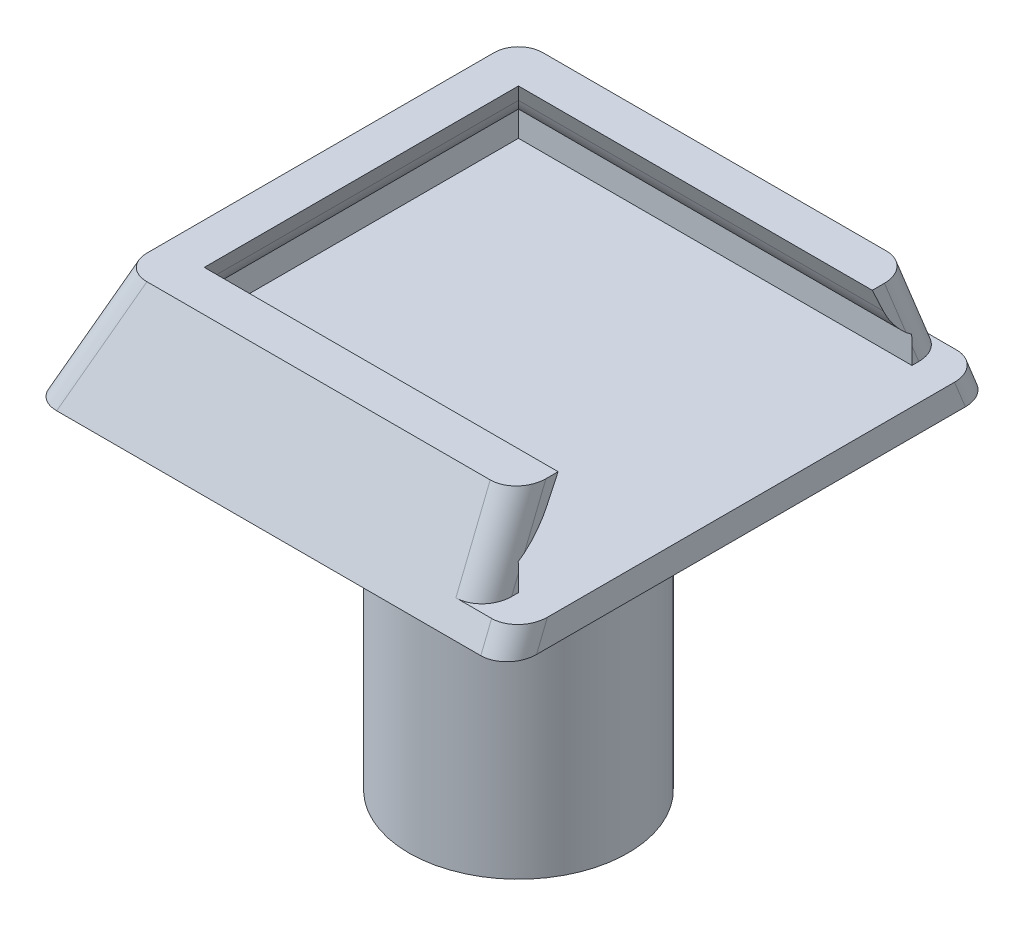
SolidWorks part; units mm, degrees
ref_plane "Front Plane" through (0, 0, 0) normal (0, 0, 1) x (1, 0, 0)
ref_plane "Top Plane" through (0, 0, 0) normal (0, 1, 0) x (1, 0, 0)
ref_plane "Right Plane" through (0, 0, 0) normal (1, 0, 0) x (0, 0, -1)
sketch "Sketch1" plane through (0, 0, 0) normal (0, 1, 0) x (1, 0, 0)
  line L1 (0, 0) -> (52, 0)
  line L2 (0, 0) -> (0, 52)
  line L3 (0, 52) -> (52, 52)
  line L4 (52, 0) -> (52, 52)
  dimension "D1" = 52
  dimension "D2" = 52
extrude "Boss-Extrude1" add sketch "Sketch1" along normal blind 3
sketch "Sketch2" plane through (0, 0, 0) normal (0, -1, 0) x (-1, 0, 0)
  line L0 (0, 0) -> (-52, 0) construction
  line L1 (0, 52) -> (0, 0) construction
  circle A0 centre (-26, 26) radius 12.25
  circle A1 centre (-26, 26) radius 10.75
  point P6 (-26, 0)
  point P9 (0, 26)
  dimension "D1" = 21.5
  dimension "D2" = 24.5
extrude "Boss-Extrude2" add sketch "Sketch2" along normal blind 38.1
sketch "Sketch4" plane through (0, 3, 0) normal (0, 1, 0) x (1, 0, 0)
  line L0 (0, 52) -> (0, 0) construction
  line L5 (52, 52) -> (0, 52) construction
  line L8 (4, 48) -> (48, 48)
  line L9 (4, 48) -> (4, 4)
  line L10 (4, 4) -> (48, 4)
  line L12 (48, 4) -> (48, 0)
  line L13 (0, 52) -> (48, 52)
  line L14 (0, 52) -> (0, 0)
  line L15 (0, 0) -> (48, 0)
  line L16 (48, 52) -> (48, 48)
  dimension "D1" = 44
  dimension "D2" = 44
  dimension "D4" = 4
  dimension "D3" = 4
extrude "Boss-Extrude3" add sketch "Sketch4" along normal blind 9.5
draft "Draft8" type of draft neutral plane draft angle 22 faces to draft 3 face at (33.3333, 5.1667, -52) face at (0, 6.25, -26) face at (33.3333, 5.1667, 0) neutral plane through (0, 3, 0) neutral plane normal (0, 1, 0) parameters "D1"=22
draft "Draft11" type of draft neutral plane draft angle 25 faces to draft 3 face at (26, 7.75, -48) face at (4, 7.75, -26) face at (26, 7.75, -4) neutral plane through (0, 3, 0) neutral plane normal (0, 1, 0) reverse direction yes parameters "D1"=25
fillet "Fillet1" radius 2 1 edges at (26, 0, -38.25)
fillet "Fillet2" radius 3 4 edges at (1.3131, 6.25, -50.6869) (48, 7.75, -50.0809) (48, 7.75, -1.9191) (1.3131, 6.25, -1.3131)
fillet "Fillet3" radius 3 2 edges at (52, 1.5, -52.606) (52, 1.5, 0.606)
sketch "Sketch5" plane through (52, 0, 0) normal (1, 0, 0) x (0, 0, -1)
  line L1 (4, 3) -> (48, 3)
  line L2 (4, 3) -> (4, 6)
  line L3 (4, 6) -> (48, 6)
  line L4 (48, 3) -> (48, 6)
  line L5 (3.2356, 3) -> (48.7644, 3) construction
  point P4 (4.5544, 3.0876)
  point P5 (47.4655, 3)
  point P6 (0, 0)
  dimension "D1" = 3
extrude "Cut-Extrude1" cut sketch "Sketch5" against normal up to vertex (48 mm away) up to point (4, 3, -4)
fillet "Fillet4" radius 10 3 edges at (26.6995, 6, -46.6011) (5.3989, 6, -26) (26.6995, 6, -5.3989)
equation "\"D1@Sketch1\"=\"D2@Sketch1\""
equation "\"D3@Sketch4\"=\"D4@Sketch4\""
